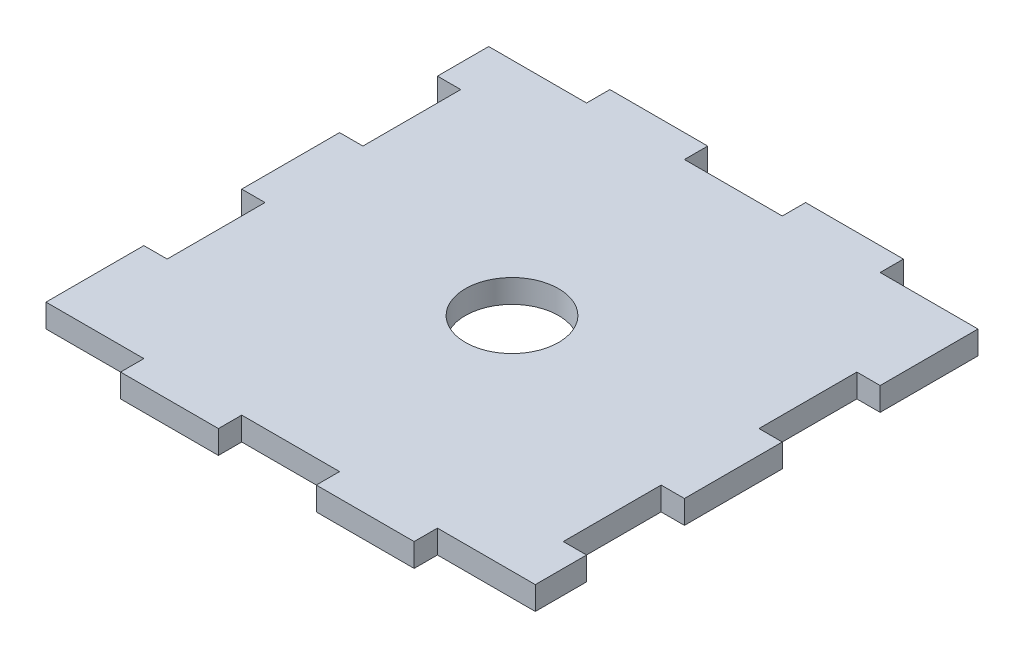
SolidWorks part; units mm, degrees
ref_plane "Front Plane" through (0, 0, 0) normal (0, 0, 1) x (1, 0, 0)
ref_plane "Top Plane" through (0, 0, 0) normal (0, 1, 0) x (1, 0, 0)
ref_plane "Right Plane" through (0, 0, 0) normal (1, 0, 0) x (0, 0, -1)
sketch "Sketch1" plane through (0, 0, 0) normal (0, 1, 0) x (1, 0, 0)
  line L1 (-50, -50) -> (50, -50)
  line L2 (-50, -50) -> (-50, 50)
  line L3 (-50, 50) -> (50, 50)
  line L4 (50, -50) -> (50, 50)
  line L5 (-50, -50) -> (50, 50) construction
  line L6 (-50, 50) -> (50, -50) construction
  point P0 (0, 0)
  dimension "D1" = 100
  dimension "D2" = 100
extrude "Boss-Extrude1" add sketch "Sketch1" along normal blind 4.7625
sketch "Sketch2" plane through (0, 4.7625, 0) normal (0, 1, 0) x (1, 0, 0)
  line L0 (50, 50) -> (-50, 50) construction
  line L1 (-45.2375, -45.2375) -> (45.2375, -45.2375)
  line L2 (-45.2375, -45.2375) -> (-45.2375, 45.2375)
  line L3 (-45.2375, 45.2375) -> (45.2375, 45.2375)
  line L4 (45.2375, -45.2375) -> (45.2375, 45.2375)
  line L5 (-45.2375, -45.2375) -> (45.2375, 45.2375) construction
  line L6 (-45.2375, 45.2375) -> (45.2375, -45.2375) construction
  line L7 (50, -50) -> (50, 50) construction
  line L8 (-10, 50) -> (-10, 45.2375)
  line L9 (-50, 50) -> (-30, 50)
  line L10 (-50, 50) -> (-50, 45.2375)
  line L11 (-50, 45.2375) -> (-30, 45.2375)
  line L12 (-30, 50) -> (-30, 45.2375)
  line L13 (-30, 50) -> (-10, 50)
  line L14 (-30, 45.2375) -> (-10, 45.2375)
  line L15 (-30, 50) -> (-30, 45.2375)
  line L16 (10, 50) -> (10, 45.2375)
  line L17 (-10, 50) -> (10, 50)
  line L18 (-10, 45.2375) -> (10, 45.2375)
  line L19 (-10, 50) -> (-10, 45.2375)
  line L20 (30, 50) -> (30, 45.2375)
  line L21 (10, 50) -> (30, 50)
  line L22 (10, 45.2375) -> (30, 45.2375)
  line L23 (10, 50) -> (10, 45.2375)
  line L24 (50, 50) -> (50, 45.2375)
  line L25 (30, 50) -> (50, 50)
  line L26 (30, 45.2375) -> (50, 45.2375)
  line L27 (30, 50) -> (30, 45.2375)
  line L28 (-30, -50) -> (-10, -50)
  line L29 (-50, -50) -> (-30, -50)
  line L30 (-50, -50) -> (-50, -45.2375)
  line L31 (-50, -45.2375) -> (-30, -45.2375)
  line L32 (-30, -50) -> (-30, -45.2375)
  line L33 (-30, -45.2375) -> (-10, -45.2375)
  line L34 (-30, -50) -> (-30, -45.2375)
  line L35 (-10, -50) -> (-10, -45.2375)
  line L36 (-10, -50) -> (10, -50)
  line L37 (-10, -45.2375) -> (10, -45.2375)
  line L38 (-10, -50) -> (-10, -45.2375)
  line L39 (10, -50) -> (10, -45.2375)
  line L40 (10, -50) -> (30, -50)
  line L41 (10, -45.2375) -> (30, -45.2375)
  line L42 (10, -50) -> (10, -45.2375)
  line L43 (30, -50) -> (30, -45.2375)
  line L44 (30, -50) -> (50, -50)
  line L45 (30, -45.2375) -> (50, -45.2375)
  line L46 (30, -50) -> (30, -45.2375)
  line L47 (50, -50) -> (50, -45.2375)
  line L48 (45.2375, 25.2375) -> (45.2375, 5.2375)
  line L49 (45.2375, 45.2375) -> (50, 45.2375)
  line L50 (45.2375, 45.2375) -> (45.2375, 25.2375)
  line L51 (45.2375, 25.2375) -> (50, 25.2375)
  line L52 (50, 45.2375) -> (50, 25.2375)
  line L53 (45.2375, 25.2375) -> (50, 25.2375)
  line L54 (50, 25.2375) -> (50, 5.2375)
  line L55 (45.2375, 5.2375) -> (50, 5.2375)
  line L56 (45.2375, 5.2375) -> (45.2375, -14.7625)
  line L57 (45.2375, 5.2375) -> (50, 5.2375)
  line L58 (50, 5.2375) -> (50, -14.7625)
  line L59 (45.2375, -14.7625) -> (50, -14.7625)
  line L60 (45.2375, -14.7625) -> (45.2375, -34.7625)
  line L61 (45.2375, -14.7625) -> (50, -14.7625)
  line L62 (50, -14.7625) -> (50, -34.7625)
  line L63 (45.2375, -34.7625) -> (50, -34.7625)
  line L64 (-50, -25.2375) -> (-50, -5.2375)
  line L65 (-50, -45.2375) -> (-45.2375, -45.2375)
  line L66 (-50, -45.2375) -> (-50, -25.2375)
  line L67 (-50, -25.2375) -> (-45.2375, -25.2375)
  line L68 (-45.2375, -45.2375) -> (-45.2375, -25.2375)
  line L69 (-50, -25.2375) -> (-45.2375, -25.2375)
  line L70 (-45.2375, -25.2375) -> (-45.2375, -5.2375)
  line L71 (-50, -5.2375) -> (-45.2375, -5.2375)
  line L72 (-50, -5.2375) -> (-50, 14.7625)
  line L73 (-50, -5.2375) -> (-45.2375, -5.2375)
  line L74 (-45.2375, -5.2375) -> (-45.2375, 14.7625)
  line L75 (-50, 14.7625) -> (-45.2375, 14.7625)
  line L76 (-50, 14.7625) -> (-50, 34.7625)
  line L77 (-50, 14.7625) -> (-45.2375, 14.7625)
  line L78 (-45.2375, 14.7625) -> (-45.2375, 34.7625)
  line L79 (-50, 34.7625) -> (-45.2375, 34.7625)
  point P0 (0, 0)
  line M5 (50, -50) -> (50, 50)
  line M6 (50, 50) -> (-50, 50)
  line M7 (-50, 50) -> (-50, -50)
  line M8 (-50, -50) -> (50, -50)
  dimension "D1" = 4.7625
  dimension "D2" = 4.7625
  dimension "D3" = 20
  dimension "D5" = 20
  dimension "D7" = 20
  dimension "D9" = 20
  dimension "D4" = 5
  dimension "D6" = 5
  dimension "D8" = 4
  dimension "D10" = 4
extrude "Cut-Extrude1" cut sketch "Sketch2" against normal blind 4.7625 contours L12 L11 L3 M6 M7 | L16 L8 L3 M6 | L3 L26 L20 M5 M6 | L4 L55 L51 M5 | L4 L63 L59 M5 | L45 L1 L43 M8 M5 | L39 L1 L35 M8 | L32 L1 L31 M8 M7 | L71 L67 L2 M7 | L79 L75 L2 M7 region at (-40, 4.7625, 47.6187) region at (-47.6188, 4.7625, 15.2375) region at (0, 4.7625, 47.6187) region at (-47.6188, 4.7625, -24.7625) region at (40, 4.7625, 47.6187) region at (-40, 4.7625, -47.6187) region at (47.6188, 4.7625, 24.7625) region at (0, 4.7625, -47.6187) region at (47.6188, 4.7625, -15.2375) region at (40, 4.7625, -47.6187)
sketch "Sketch3" plane through (0, 4.7625, 0) normal (0, 1, 0) x (1, 0, 0)
  line L0 (0, -45.2375) -> (0, 45.2375) construction
  line L1 (-10, -45.2375) -> (10, -45.2375) construction
  line L2 (-10, 45.2375) -> (10, 45.2375) construction
  circle A0 centre (0, 0) radius 9.525
  point P8 (0, 0)
  dimension "D1" = 19.05
extrude "Cut-Extrude2" cut sketch "Sketch3" against normal through all contours A0
